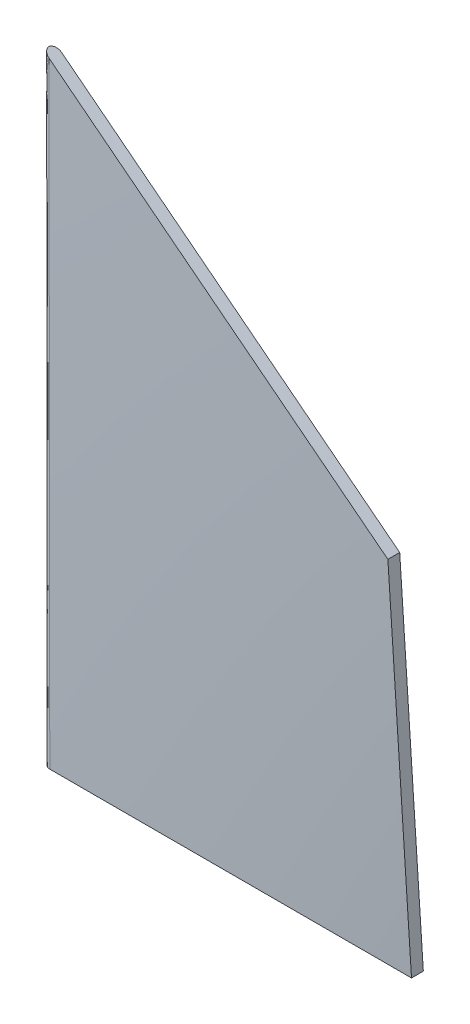
SolidWorks part; units mm, degrees
material "Verre"
ref_plane "Plan de face" through (0, 0, 0) normal (0, 0, 1) x (1, 0, 0)
ref_plane "Plan de dessus" through (0, 0, 0) normal (0, 1, 0) x (1, 0, 0)
ref_plane "Plan de droite" through (0, 0, 0) normal (1, 0, 0) x (0, 0, -1)
sketch "Esquisse1" plane through (0, 0, 0) normal (1, 0, 0) x (0, 0, -1)
  line L1 (311.9526, 1025.8054) -> (356.9526, 1025.8054)
  line L2 (311.9526, 1025.8054) -> (311.9526, -1330.7746)
  line L3 (311.9526, -1330.7746) -> (356.9526, -1330.7746)
  line L4 (356.9526, 1025.8054) -> (356.9526, -1330.7746)
  dimension "D1" = 2356.58
  dimension "D2" = 45
ref_plane "Plan1" through (1400, 0, 0) normal (1, 0, 0) x (0, 0, -1)
sketch "Esquisse2" plane through (1400, 0, 0) normal (1, 0, 0) x (0, 0, -1)
  line L0 (311.9526, -1330.7746) -> (356.9526, -1330.7746)
  line L1 (356.9526, -1330.7746) -> (267.1605, 92.4657)
  line L2 (267.1605, 92.4657) -> (222.1605, 92.4657)
  line L3 (222.1605, 92.4657) -> (311.9526, -1330.7746)
  dimension "D1" = 1426.07
  dimension "D2" = 86.39
  dimension "D3" = 45
loft "Lissage1" add profiles "Esquisse1", "Esquisse2" connector at (0, 1025.8054, -356.9526) connector at (1400, 92.4657, -267.1605)
sketch "Esquisse3" plane through (0, -1330.7746, 0) normal (0, -1, 0) x (1, 0, 0)
  line L1 (0, -311.9526) -> (1400, -311.9526) construction
  line L2 (0, -311.9526) -> (0, -356.9526) construction
  circle A0 centre (10, -334.4526) radius 5
  dimension "D1" = 10
  dimension "D2" = 10
  dimension "D3" = 22.5
extrude "Enlèv. mat.-Extru.1" cut sketch "Esquisse3" against normal blind 20
fillet "Congé1" radius 25 2 edges
